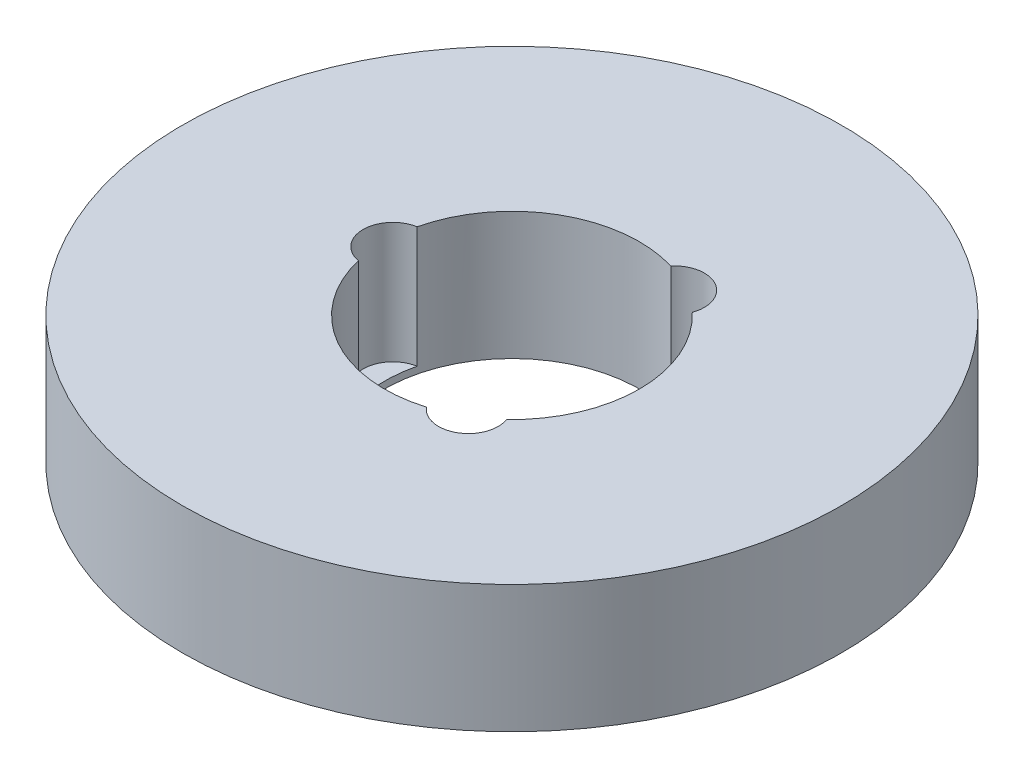
SolidWorks part; units mm, degrees
ref_plane "Front Plane" through (0, 0, 0) normal (0, 0, 1) x (1, 0, 0)
ref_plane "Top Plane" through (0, 0, 0) normal (0, 1, 0) x (1, 0, 0)
ref_plane "Right Plane" through (0, 0, 0) normal (1, 0, 0) x (0, 0, -1)
sketch "Sketch1" plane through (0, 0, 0) normal (0, 1, 0) x (1, 0, 0)
  circle A0 centre (0, 0) radius 77.5
  dimension "FLANGE_OD" = 155
extrude "Boss-Extrude1" add sketch "Sketch1" along normal blind 30
sketch "Sketch2" plane through (0, 0, 0) normal (0, 1, 0) x (1, 0, 0)
  circle A0 centre (0, 0) radius 30
  dimension "BORE_D" = 60
extrude "Cut-Extrude1" cut sketch "Sketch2" along normal through all
sketch "Sketch3" plane through (0, 30, 0) normal (0, 1, 0) x (1, 0, 0)
  circle A0 centre (0, 0) radius 27.9893 construction
  circle A1 centre (-27.9893, 0) radius 7.0085
  dimension "BOLT_D" = 14.017
  dimension "BOLT_PCD" = 55.9786
extrude "Cut-Extrude2" cut sketch "Sketch3" against normal blind 28.3998
pattern_circular "CirPattern1" count 3 over 360 about axis through (0, 0, 0) along (0, 1, 0) of "Cut-Extrude2"
